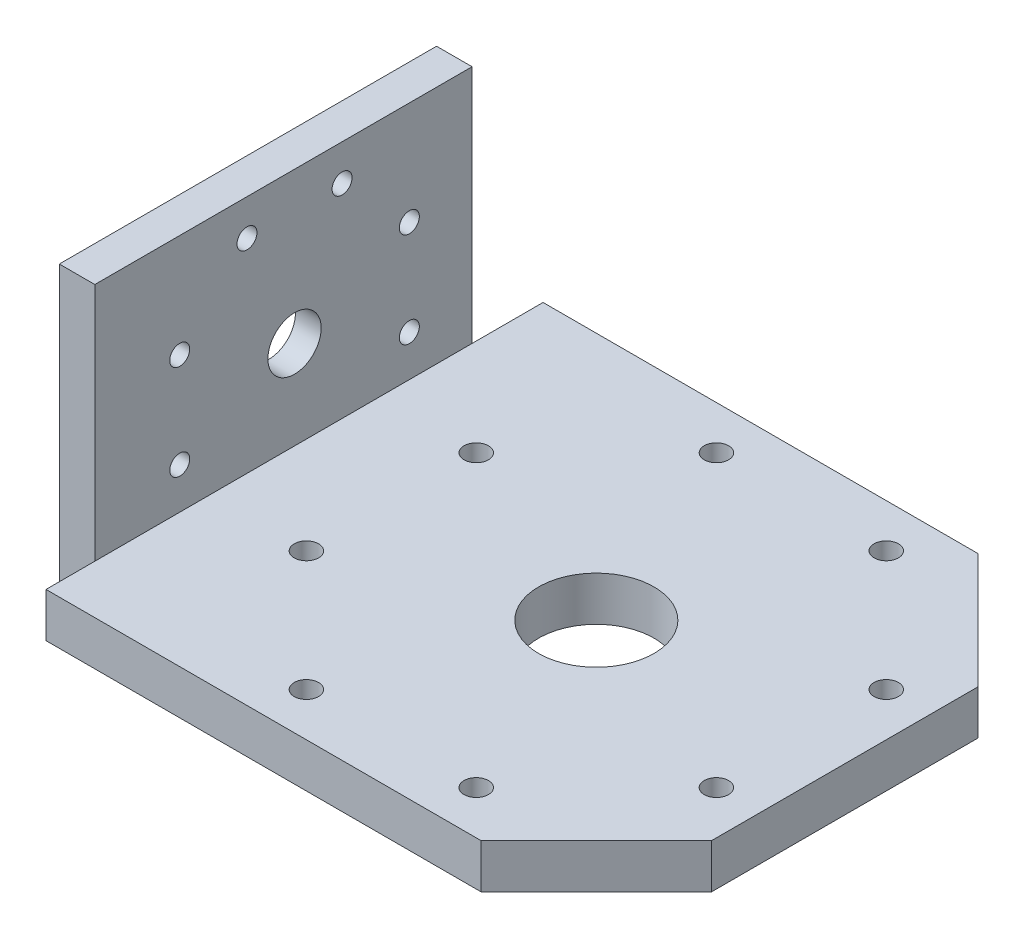
SolidWorks part; units mm, degrees
material "6061-T6 (SS)"
ref_plane "Front Plane" through (0, 0, 0) normal (0, 0, 1) x (1, 0, 0)
ref_plane "Top Plane" through (0, 0, 0) normal (0, 1, 0) x (1, 0, 0)
ref_plane "Right Plane" through (0, 0, 0) normal (1, 0, 0) x (0, 0, -1)
ref_plane "PL_Back_Plate_base" through (-76, 0, 0) normal (1, 0, 0) x (0, 0, -1)
sketch "SK_Back_Plate" plane through (-76, 0, 0) normal (1, 0, 0) x (0, 0, -1)
  line L0 (40, -36) -> (40, 34)
  line L1 (40, 34) -> (-45, 34)
  line L2 (-45, 34) -> (-45, -36)
  line L3 (-45, -36) -> (40, -36)
  circle A0 centre (25.8686, 10.7151) radius 2.25
  circle A1 centre (10.7151, 25.8686) radius 2.25
  circle A2 centre (-10.7151, 25.8686) radius 2.25
  circle A3 centre (-25.8686, 10.7151) radius 2.25
  circle A4 centre (-25.8686, -10.7151) radius 2.25
  circle A5 centre (-10.7151, -25.8686) radius 2.25
  circle A6 centre (10.7151, -25.8686) radius 2.25
  circle A7 centre (25.8686, -10.7151) radius 2.25
  circle A8 centre (0, 0) radius 6
  dimension "D9_SK_Back_Plate" = 4.5
  dimension "D12_SK_Back_Plate" = 4.5
  dimension "D15_SK_Back_Plate" = 4.5
  dimension "D18_SK_Back_Plate" = 4.5
  dimension "D21_SK_Back_Plate" = 4.5
  dimension "D24_SK_Back_Plate" = 4.5
  dimension "D27_SK_Back_Plate" = 4.5
  dimension "D30_SK_Back_Plate" = 4.5
  dimension "D33_SK_Back_Plate" = 12
  dimension "P1" = 40
  dimension "P2" = 36
  dimension "P3" = 40
  dimension "P4" = 34
  dimension "P5" = 45
  dimension "P6" = 34
  dimension "P7" = 45
  dimension "P8" = 36
  dimension "P10" = 25.8686
  dimension "P11" = 10.7151
  dimension "P13" = 10.7151
  dimension "P14" = 25.8686
  dimension "P16" = 10.7151
  dimension "P17" = 25.8686
  dimension "P19" = 25.8686
  dimension "P20" = 10.7151
  dimension "P22" = 25.8686
  dimension "P23" = 10.7151
  dimension "P25" = 10.7151
  dimension "P26" = 25.8686
  dimension "P28" = 10.7151
  dimension "P29" = 25.8686
  dimension "P31" = 25.8686
  dimension "P32" = 10.7151
extrude "Back_Plate" add sketch "SK_Back_Plate" along normal blind 8
ref_plane "PL_Roll_Pilot_Recess_base" through (-76, 0, 0) normal (1, 0, 0) x (0, 0, -1)
sketch "SK_Roll_Pilot_Recess" plane through (-76, 0, 0) normal (1, 0, 0) x (0, 0, -1)
  circle A0 centre (0, 0) radius 22.15
  dimension "D1_SK_Roll_Pilot_Recess" = 44.3
extrude "Roll_Pilot_Recess" cut sketch "SK_Roll_Pilot_Recess" along normal blind 2.2
ref_plane "PL_Medial_Plate_base" through (0, -30, 0) normal (0, 1, 0) x (1, 0, 0)
sketch "SK_Medial_Plate" plane through (0, -30, 0) normal (0, 1, 0) x (1, 0, 0)
  line L0 (-68, 56) -> (30, 56)
  line L1 (30, 56) -> (56, 30)
  line L2 (56, 30) -> (56, -30)
  line L3 (56, -30) -> (30, -56)
  line L4 (30, -56) -> (-68, -56)
  line L5 (-68, -56) -> (-68, 56)
  circle A0 centre (46.194, 19.1342) radius 2.75
  circle A1 centre (19.1342, 46.194) radius 2.75
  circle A2 centre (-19.1342, 46.194) radius 2.75
  circle A3 centre (-46.194, 19.1342) radius 2.75
  circle A4 centre (-46.194, -19.1342) radius 2.75
  circle A5 centre (-19.1342, -46.194) radius 2.75
  circle A6 centre (19.1342, -46.194) radius 2.75
  circle A7 centre (46.194, -19.1342) radius 2.75
  circle A8 centre (0, 0) radius 13
  dimension "D13_SK_Medial_Plate" = 5.5
  dimension "D16_SK_Medial_Plate" = 5.5
  dimension "D19_SK_Medial_Plate" = 5.5
  dimension "D22_SK_Medial_Plate" = 5.5
  dimension "D25_SK_Medial_Plate" = 5.5
  dimension "D28_SK_Medial_Plate" = 5.5
  dimension "D31_SK_Medial_Plate" = 5.5
  dimension "D34_SK_Medial_Plate" = 5.5
  dimension "D37_SK_Medial_Plate" = 26
  dimension "P1" = 68
  dimension "P2" = 56
  dimension "P3" = 30
  dimension "P4" = 56
  dimension "P5" = 56
  dimension "P6" = 30
  dimension "P7" = 56
  dimension "P8" = 30
  dimension "P9" = 30
  dimension "P10" = 56
  dimension "P11" = 68
  dimension "P12" = 56
  dimension "P14" = 46.194
  dimension "P15" = 19.1342
  dimension "P17" = 19.1342
  dimension "P18" = 46.194
  dimension "P20" = 19.1342
  dimension "P21" = 46.194
  dimension "P23" = 46.194
  dimension "P24" = 19.1342
  dimension "P26" = 46.194
  dimension "P27" = 19.1342
  dimension "P29" = 19.1342
  dimension "P30" = 46.194
  dimension "P32" = 19.1342
  dimension "P33" = 46.194
  dimension "P35" = 46.194
  dimension "P36" = 19.1342
extrude "Medial_Plate" add sketch "SK_Medial_Plate" along normal blind 10
equation "\"Roll_face_x\"= -76"
equation "\"Pitch_rear_y\"= -20"
equation "\"Plate_t\"= 10"
equation "\"Back_bottom_z\"= -40"
